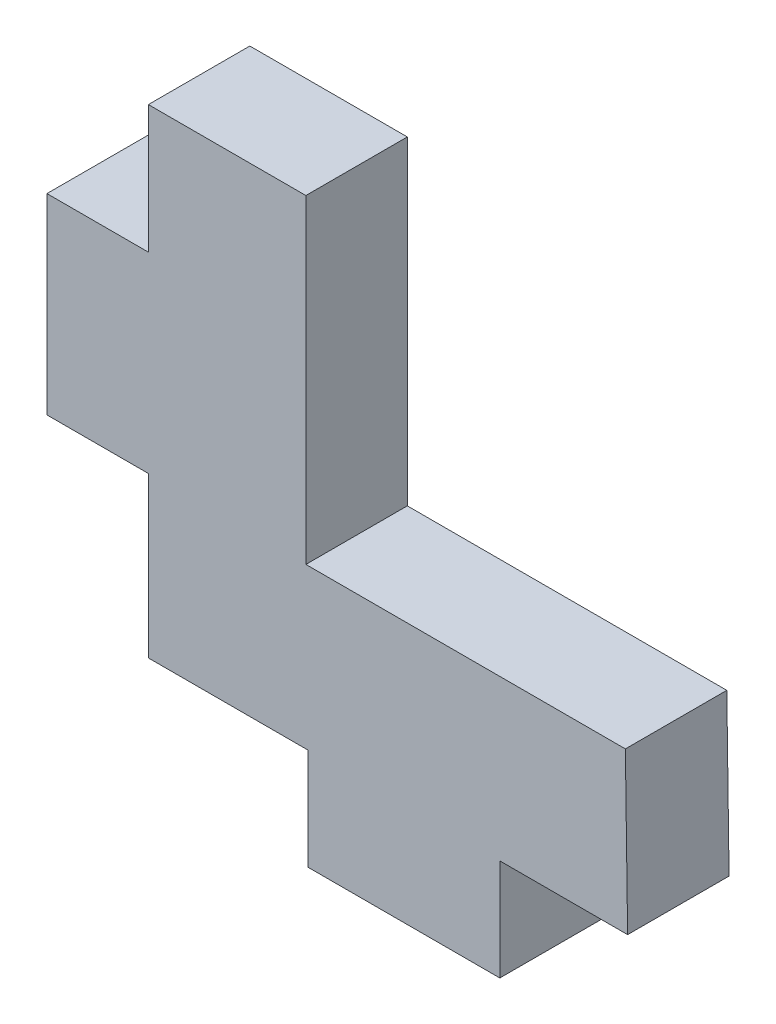
SolidWorks part; units mm, degrees
ref_plane "Front Plane" through (0, 0, 0) normal (0, 0, 1) x (1, 0, 0)
ref_plane "Top Plane" through (0, 0, 0) normal (0, 1, 0) x (1, 0, 0)
ref_plane "Right Plane" through (0, 0, 0) normal (1, 0, 0) x (0, 0, -1)
sketch "Sketch1" plane through (0, 0, 0) normal (0, 0, 1) x (1, 0, 0)
  line L0 (0, 0) -> (0, 5)
  line L1 (0, 5) -> (-3.175, 5)
  line L2 (-3.175, 5) -> (-3.175, 11)
  line L3 (-3.175, 11) -> (0, 11)
  line L4 (0, 11) -> (0, 15)
  line L5 (0, 15) -> (4.9295, 15)
  line L6 (4.9295, 15) -> (4.9295, 5)
  line L7 (4.9295, 5) -> (14.9295, 5)
  line L8 (14.9295, 5) -> (15, 0)
  line L9 (15, 0) -> (11, 0)
  line L10 (11, 0) -> (11, -3.175)
  line L11 (11, -3.175) -> (5, -3.175)
  line L12 (5, -3.175) -> (5, 0)
  line L13 (5, 0) -> (0, 0)
  dimension "D1" = 6
  dimension "D2" = 3.175
  dimension "D3" = 15
  dimension "D4" = 10
  dimension "D5" = 5
extrude "Boss-Extrude1" add sketch "Sketch1" along normal mid plane 3.175
